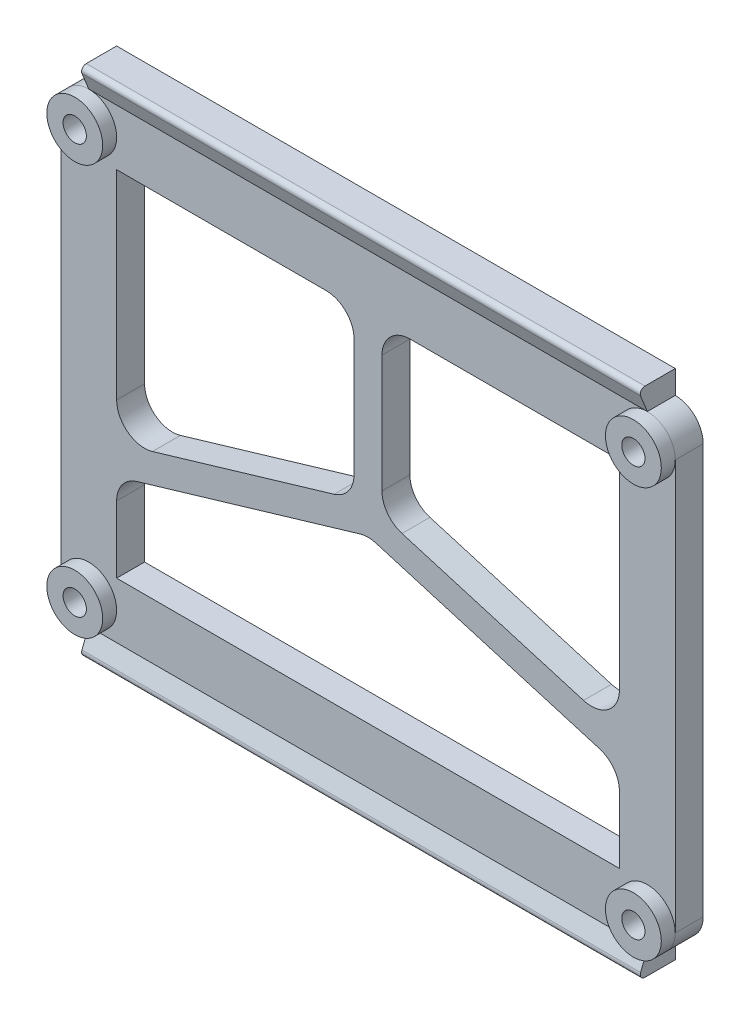
SolidWorks part; units mm, degrees
ref_plane "Front Plane" through (0, 0, 0) normal (0, 0, 1) x (1, 0, 0)
ref_plane "Top Plane" through (0, 0, 0) normal (0, 1, 0) x (1, 0, 0)
ref_plane "Right Plane" through (0, 0, 0) normal (1, 0, 0) x (0, 0, -1)
sketch "ODrive Mounting Holes" plane through (0, 0, 0) normal (0, 0, 1) x (1, 0, 0)
  line L0 (-30, 22) -> (30, -22) construction
  line L1 (-30, 22) -> (30, 22) construction
  line L2 (-30, 22) -> (-30, -22) construction
  line L3 (-30, -22) -> (30, -22) construction
  line L4 (30, 22) -> (30, -22) construction
  dimension "D1" = 44
  dimension "D2" = 60
sketch "Sketch2" plane through (0, 0, 0) normal (0, 0, 1) x (1, 0, 0)
  line L14 (-33, -25) -> (33, -25)
  line L15 (33, -25) -> (33, 25)
  line L16 (-33, 25) -> (-33, -25)
  line L17 (33, 25) -> (-33, 25)
  line L18 (-33, -25) -> (33, -25)
  line L19 (33, -25) -> (33, 25)
  line L20 (-33, 25) -> (-33, -25)
  line L21 (33, 25) -> (-33, 25)
  dimension "D1" = 3
extrude "Boss-Extrude1" add sketch "Sketch2" along normal blind 3
sketch "Sketch3" plane through (0, 0, 3) normal (0, 0, 1) x (1, 0, 0)
  circle A0 centre (-30, 22) radius 1.25
  circle A1 centre (30, 22) radius 1.25
  circle A2 centre (30, -22) radius 1.25
  circle A3 centre (-30, -22) radius 1.25
  dimension "D1" = 2.5
extrude "Cut-Extrude1" cut sketch "Sketch3" against normal blind 3
sketch "Sketch4" plane through (0, 0, 0) normal (0, 0, -1) x (-1, 0, 0)
  line L0 (30, 24.4249) -> (32.1, 23.2124)
  line L1 (32.1, 23.2124) -> (32.1, 20.7876)
  line L2 (32.1, 20.7876) -> (30, 19.5751)
  line L4 (30, 19.5751) -> (27.9, 20.7876)
  line L5 (27.9, 20.7876) -> (27.9, 23.2124)
  line L6 (27.9, 23.2124) -> (30, 24.4249)
  line L7 (30, 24.4249) -> (30, 19.5751) construction
  line L8 (-30, 24.4249) -> (-27.9, 23.2124)
  line L9 (-27.9, 23.2124) -> (-27.9, 20.7876)
  line L10 (-27.9, 20.7876) -> (-30, 19.5751)
  line L11 (-30, 19.5751) -> (-32.1, 20.7876)
  line L12 (-32.1, 20.7876) -> (-32.1, 23.2124)
  line L13 (-32.1, 23.2124) -> (-30, 24.4249)
  line L14 (-30, 24.4249) -> (-30, 19.5751) construction
  line L15 (-30, -19.5751) -> (-27.9, -20.7876)
  line L16 (-27.9, -20.7876) -> (-27.9, -23.2124)
  line L17 (-27.9, -23.2124) -> (-30, -24.4249)
  line L18 (-30, -24.4249) -> (-32.1, -23.2124)
  line L19 (-32.1, -23.2124) -> (-32.1, -20.7876)
  line L20 (-32.1, -20.7876) -> (-30, -19.5751)
  line L21 (-30, -19.5751) -> (-30, -24.4249) construction
  line L22 (30, -19.5751) -> (32.1, -20.7876)
  line L23 (32.1, -20.7876) -> (32.1, -23.2124)
  line L24 (32.1, -23.2124) -> (30, -24.4249)
  line L25 (30, -24.4249) -> (27.9, -23.2124)
  line L26 (27.9, -23.2124) -> (27.9, -20.7876)
  line L27 (27.9, -20.7876) -> (30, -19.5751)
  line L28 (30, -19.5751) -> (30, -24.4249) construction
  dimension "D1" = 120
  dimension "D2" = 120
  dimension "D3" = 4.2
  dimension "D4" = 2
  dimension "D5" = 2
extrude "Cut-Extrude2" cut sketch "Sketch4" against normal blind 1.5
sketch "Sketch5" plane through (0, 0, 0) normal (0, 0, -1) x (-1, 0, 0)
  line L0 (0, 19) -> (0, 0) construction
  line L1 (0, 0) -> (-27, -8) construction
  line L2 (0, 0) -> (27, -8) construction
  line L3 (-1.5, 19) -> (-1.5, 1.12)
  line L4 (-1.5, 1.12) -> (-27, -6.4355)
  line L5 (0, -1.5645) -> (27, -9.5645)
  line L6 (1.5, 19) -> (1.5, 1.12)
  line L7 (0, -1.5645) -> (-27, -9.5645)
  line L8 (1.5, 1.12) -> (27, -6.4355)
  line L9 (-0.4261, 1.4382) -> (-27.4261, -6.5618) construction
  line L10 (0.4261, -1.4382) -> (-26.5739, -9.4382) construction
  line L11 (0.4261, 1.4382) -> (27.4261, -6.5618) construction
  line L12 (-0.4261, -1.4382) -> (26.5739, -9.4382) construction
  line L13 (-1.5, 19) -> (-1.5, 0) construction
  line L14 (27, -19) -> (27, 19)
  line L15 (-27, -19) -> (27, -19)
  line L16 (-27, 19) -> (-27, -19)
  line L17 (27, 19) -> (-27, 19)
  line L18 (27, -19) -> (27, 19)
  line L19 (-27, -19) -> (27, -19)
  line L20 (-27, 19) -> (-27, -19)
  line L21 (27, 19) -> (-27, 19)
  line L22 (1.5, 19) -> (1.5, 0) construction
  point P2 (-27, 0)
  dimension "D2" = 8
  dimension "D1" = 6
  dimension "D3" = 1.5
  dimension "D4" = 1.5
extrude "Cut-Extrude3" cut sketch "Sketch5" against normal through all contours L3 L21 L20 L4 | L18 L21 L6 L8 | L7 L20 L19 L18 L5 region at (14.9913, 8.0613, 0) region at (-14.9913, 8.0613, 0) region at (0, -12.0838, 0)
sketch "Sketch6" plane through (0, 0, 3) normal (0, 0, 1) x (1, 0, 0)
  circle A0 centre (30, 22) radius 3
  circle A1 centre (-30, 22) radius 3
  circle A2 centre (-30, -22) radius 3
  circle A3 centre (30, -22) radius 3
  circle A4 centre (-30, 22) radius 1.25
  circle A5 centre (30, 22) radius 1.25
  circle A6 centre (30, -22) radius 1.25
  circle A7 centre (-30, -22) radius 1.25
  dimension "D1" = 6
  dimension "D2" = 2.5
extrude "Boss-Extrude2" add sketch "Sketch6" along normal blind 1.5
fillet "Fillet1" radius 3 13 edges at (27, -9.5645, 1.5) (-27, -9.5645, 1.5) (-27, -6.4355, 1.5) (27, -6.4355, 1.5) (0, -1.5645, 1.5) (1.5, 1.12, 1.5) (-1.5, 1.12, 1.5) (1.5, 19, 1.5) (-1.5, 19, 1.5) (-33, 25, 1.5) (-33, -25, 1.5) (33, -25, 1.5) (33, 25, 1.5)
sketch "Sketch7" plane through (0, 0, 0) normal (1, 0, 0) x (0, 0, -1)
  line L0 (0, 25) -> (0, 27.5)
  line L1 (0, 27.5) -> (-4, 27.5)
  line L2 (-4, 27.5) -> (-3, 25)
  line L3 (-3, 25) -> (0, 25)
  dimension "D1" = 2.5
  dimension "D2" = 4
extrude "Boss-Extrude3" add sketch "Sketch7" along normal mid plane 60
fillet "Fillet2" radius 0.5 1 edges at (0, 27.5, 4)
mirror "Mirror1" about plane through (0, 0, 0) normal (0, 1, 0) of "Boss-Extrude3", "Fillet2"
